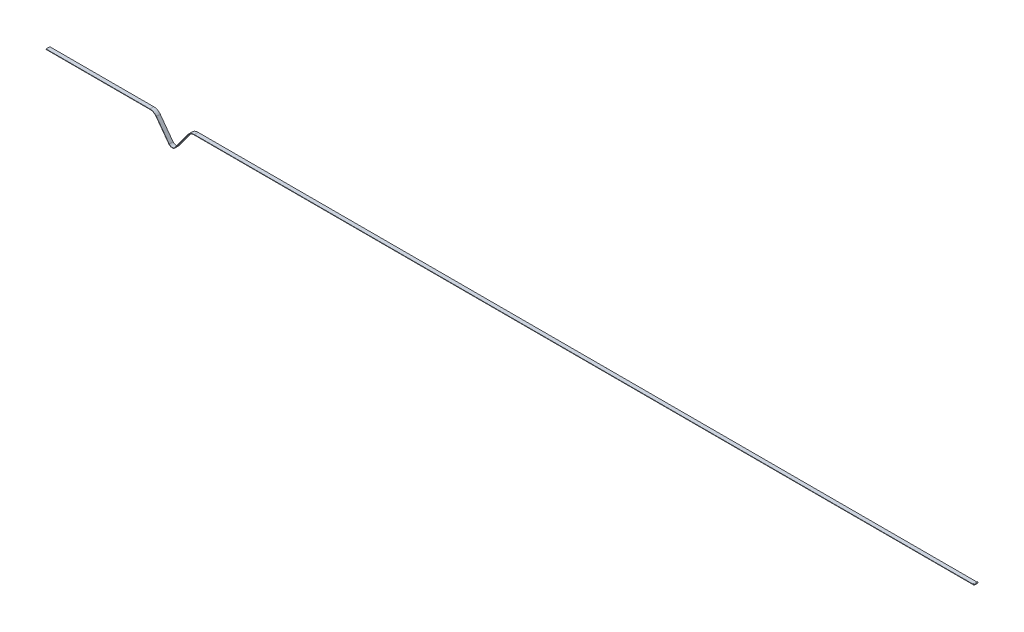
SolidWorks part; units mm, degrees
material "BUTYL"
ref_plane "Front Plane" through (0, 0, 0) normal (0, 0, 1) x (1, 0, 0)
ref_plane "Top Plane" through (0, 0, 0) normal (0, 1, 0) x (1, 0, 0)
ref_plane "Right Plane" through (0, 0, 0) normal (1, 0, 0) x (0, 0, -1)
sketch "Sketch1" plane through (0, 0, 0) normal (1, 0, 0) x (0, 0, -1)
  line L1 (0, 0) -> (6, 0)
  line L2 (0, 0) -> (0, 0.63)
  line L3 (0, 0.63) -> (6, 0.63)
  line L4 (6, 0) -> (6, 0.63)
  dimension "D1" = 0.63
  dimension "D2" = 6
sketch "Sketch2" plane through (0, 0, 0) normal (0, 0, 1) x (1, 0, 0)
  line L0 (0, 0) -> (-1216.5422, 0)
  line L1 (-1226.1749, -4.8779) -> (-1246.187, -32.1359)
  line L2 (-1256.0374, -32.1359) -> (-1276.0495, -4.8779)
  line L3 (-1285.6822, 0) -> (-1447.8, 0)
  arc A0 (-1216.5422, 0) -> (-1226.1749, -4.8779) centre (-1216.5422, -11.95) ccw
  arc A1 (-1246.187, -32.1359) -> (-1256.0374, -32.1359) centre (-1251.1122, -28.52) cw
  arc A2 (-1276.0495, -4.8779) -> (-1285.6822, 0) centre (-1285.6822, -11.95) ccw
  circle A3 centre (-1251.1122, -28.52) radius 8 construction
  circle A4 centre (-1216.5422, -11.95) radius 11.95 construction
  circle A5 centre (-1285.6822, -11.95) radius 11.95 construction
  dimension "D1" = 6.11
  dimension "D4" = 1447.8
sweep "Sweep1" add profiles "Sketch1" path "Sketch2"
sketch "Sketch3" plane through (0, 0, 0) normal (0, 0, 1) x (1, 0, 0)
  line L0 (0, 0.63) -> (-1216.5422, 0.63) construction
  line L1 (-1.5, 0.63) -> (-1.5, 0)
  line L2 (0, 0) -> (-1216.5422, 0) construction
  line L3 (-1.5, 0) -> (0, 0)
  line L4 (0, 0) -> (0, 0.63)
  arc A1 (0, 0.63) -> (-1.5, 0.63) centre (-0.75, 0.63) ccw
  dimension "D1" = 0.75
extrude "Boss-Extrude1" add sketch "Sketch3" against normal through all
pattern_curve "CrvPattern1" [suppressed] of bodies 102 driven by "Sketch2" parameters "D1"=2000, "D3"=2, "D2"=1, "D4"=10
